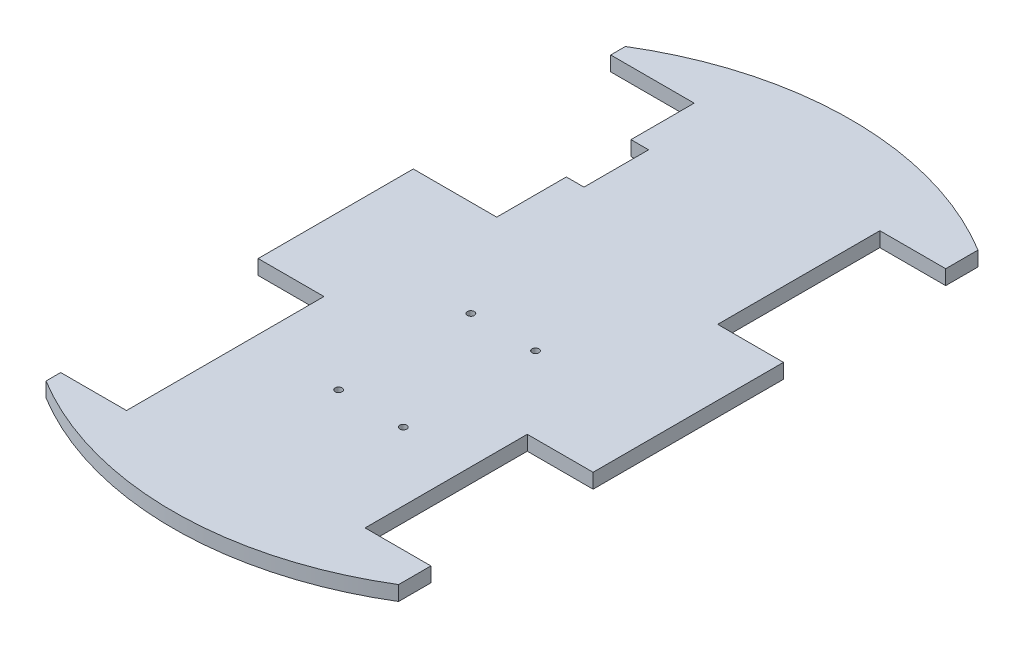
SolidWorks part; units mm, degrees
material "Oak"
ref_plane "Front Plane" through (0, 0, 0) normal (0, 0, 1) x (1, 0, 0)
ref_plane "Top Plane" through (0, 0, 0) normal (0, 1, 0) x (1, 0, 0)
ref_plane "Right Plane" through (0, 0, 0) normal (1, 0, 0) x (0, 0, -1)
sketch "Sketch1" plane through (0, 0, 0) normal (0, 1, 0) x (1, 0, 0)
  line L0 (50.292, 32.512) -> (76.2, 32.512) construction
  line L1 (-76.2, 32.512) -> (-50.292, 32.512) construction
  line L2 (-76.2, 32.512) -> (-76.2, -32.512) construction
  line L3 (-76.2, -32.512) -> (-50.292, -32.512) construction
  line L4 (-50.292, 32.512) -> (-50.292, -32.512) construction
  line L5 (-76.2, 32.512) -> (-50.292, -32.512) construction
  line L6 (-76.2, -32.512) -> (-50.292, 32.512) construction
  line L7 (50.292, 32.512) -> (50.292, -32.512) construction
  line L8 (50.292, -32.512) -> (76.2, -32.512) construction
  line L9 (76.2, 32.512) -> (76.2, -32.512) construction
  line L10 (50.292, 32.512) -> (76.2, -32.512) construction
  line L11 (50.292, -32.512) -> (76.2, 32.512) construction
  line L12 (-76.2, -119.888) -> (-50.292, -119.888) construction
  line L13 (-76.2, -119.888) -> (-76.2, -184.912) construction
  line L14 (-76.2, -184.912) -> (-50.292, -184.912) construction
  line L15 (-50.292, -119.888) -> (-50.292, -184.912) construction
  line L16 (-76.2, -119.888) -> (-50.292, -184.912) construction
  line L17 (-76.2, -184.912) -> (-50.292, -119.888) construction
  line L18 (50.292, -119.888) -> (76.2, -119.888) construction
  line L19 (50.292, -119.888) -> (50.292, -184.912) construction
  line L20 (50.292, -184.912) -> (76.2, -184.912) construction
  line L21 (76.2, -119.888) -> (76.2, -184.912) construction
  line L22 (50.292, -119.888) -> (76.2, -184.912) construction
  line L23 (50.292, -184.912) -> (76.2, -119.888) construction
  line L24 (-76.2, -42.672) -> (-40.132, -42.672)
  line L25 (-76.2, 0) -> (76.2, 0) construction
  line L26 (-76.2, 0) -> (-76.2, -152.4) construction
  line L27 (-76.2, -152.4) -> (76.2, -152.4) construction
  line L28 (76.2, 0) -> (76.2, -152.4) construction
  line L29 (-76.2, 0) -> (76.2, -152.4) construction
  line L30 (-76.2, -152.4) -> (76.2, 0) construction
  line L31 (-40.132, 42.672) -> (-40.132, -42.672)
  line L32 (-76.2, 42.672) -> (-40.132, 42.672)
  line L33 (47.752, -35.052) -> (76.2, -35.052)
  line L34 (47.752, 35.052) -> (47.752, -35.052)
  line L35 (47.752, 35.052) -> (76.2, 35.052)
  line L36 (47.752, -187.452) -> (76.2, -187.452)
  line L37 (47.752, -117.348) -> (47.752, -187.452)
  line L38 (47.752, -117.348) -> (76.2, -117.348)
  line L39 (-76.2, -195.072) -> (-47.752, -195.072)
  line L40 (-47.752, -109.728) -> (-47.752, -195.072)
  line L41 (-76.2, -109.728) -> (-47.752, -109.728)
  line L42 (-76.2, -109.728) -> (-76.2, -42.672)
  line L43 (76.2, -35.052) -> (76.2, -117.348)
  line L44 (-76.2, 42.672) -> (-76.2, 49.022)
  line L45 (76.2, 35.052) -> (76.2, 49.022)
  line L46 (-76.2, -195.072) -> (-76.2, -201.422)
  line L47 (76.2, -187.452) -> (76.2, -201.422)
  line L48 (0, 0) -> (0, 19.7922) construction
  line L49 (-32.512, 15.3535) -> (-40.132, 15.3535)
  line L50 (-32.512, 15.3535) -> (-32.512, -12.5865)
  line L51 (-32.512, -12.5865) -> (-40.132, -12.5865)
  line L52 (-40.132, 15.3535) -> (-40.132, -12.5865)
  line L53 (-32.512, 15.3535) -> (-40.132, -12.5865) construction
  line L54 (-32.512, -12.5865) -> (-40.132, 15.3535) construction
  line L55 (32.512, -12.5865) -> (40.132, -12.5865)
  line L56 (32.512, 15.3535) -> (32.512, -12.5865)
  line L57 (32.512, 15.3535) -> (40.132, 15.3535)
  arc A0 (-76.2, 49.022) -> (76.2, 49.022) centre (0, -76.2) cw
  arc A1 (-76.2, -201.422) -> (76.2, -201.422) centre (0, -76.2) ccw
  point P4 (-63.246, 0)
  point P9 (63.246, 0)
  point P14 (-63.246, -152.4)
  point P19 (63.246, -152.4)
  point P24 (0, -76.2)
  point P52 (-36.322, 1.3835)
  dimension "D7" = 6.35
  dimension "D8" = 7.62
  dimension "D12" = 146.5844
  dimension "D1" = 152.4
  dimension "D2" = 152.4
  dimension "D3" = 25.908
  dimension "D4" = 65.024
  dimension "D6" = 2.54
  dimension "D9" = 27.94
  dimension "D10" = 10.16
  dimension "D5" = 10.16
  dimension "D11" = 10.16
  dimension "D13" = 2.54
  dimension "D14" = 67.056
  dimension "D15" = 28.448
  dimension "D16" = 77.5894
extrude "Chassis" add sketch "Sketch1" along normal blind 6.35 contours L46 A1 L47 L36 L37 L38 L43 L33 L34 L55 L56 L57 L35 L45 A0 L44 L32 L31 L49 L50 L51 L24 L42 L41 L40 L39 region at (2.7397, 0, 78.2102)
sketch "Sketch2" plane through (0, 6.35, 0) normal (0, 1, 0) x (1, 0, 0)
  line L0 (-47.752, -109.728) -> (-47.752, -195.072) construction
  line L1 (-76.2, -109.728) -> (-47.752, -109.728) construction
  circle A0 centre (18.288, -84.328) radius 1.5
  circle A1 centre (-9.652, -84.328) radius 1.5
  circle A2 centre (-9.652, -141.478) radius 1.5
  circle A3 centre (18.288, -141.478) radius 1.5
  dimension "D1" = 3
  dimension "D2" = 3
  dimension "D3" = 3
  dimension "D4" = 3
  dimension "D5" = 57.15
  dimension "D6" = 27.94
  dimension "D7" = 38.1
  dimension "D8" = 31.75
extrude "Cut-Extrude1" cut sketch "Sketch2" against normal blind 12.7
